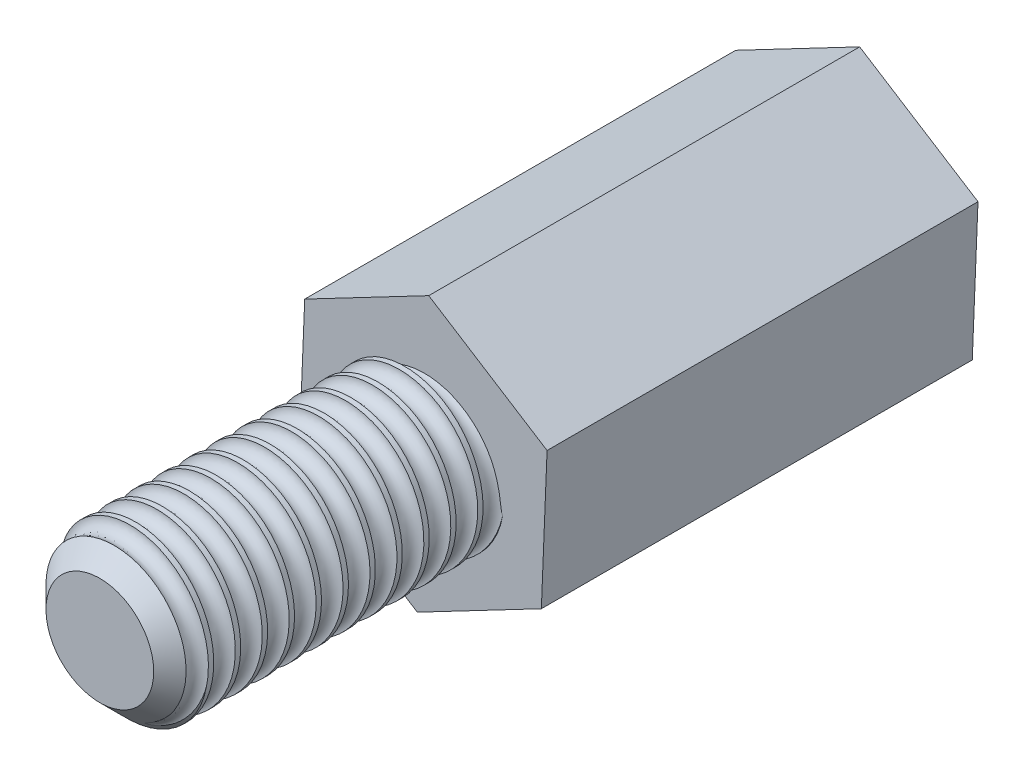
SolidWorks part; units mm, degrees
ref_plane "前视基准面" through (0, 0, 0) normal (0, 0, 1) x (1, 0, 0)
ref_plane "上视基准面" through (0, 0, 0) normal (0, 1, 0) x (1, 0, 0)
ref_plane "右视基准面" through (0, 0, 0) normal (1, 0, 0) x (0, 0, -1)
sketch "草图1" plane through (0, 0, 0) normal (0, 0, 1) x (1, 0, 0)
  line L1 (2.3029, 1.2069) -> (0.1062, 2.5978)
  line L2 (0.1062, 2.5978) -> (-2.1967, 1.3909)
  line L3 (-2.1967, 1.3909) -> (-2.3029, -1.2069)
  line L4 (-2.3029, -1.2069) -> (-0.1062, -2.5978)
  line L5 (-0.1062, -2.5978) -> (2.1967, -1.3909)
  line L6 (2.1967, -1.3909) -> (2.3029, 1.2069)
  circle A0 centre (0, 0) radius 2.6 construction
  dimension "D1" = 5.2
extrude "凸台-拉伸1" add sketch "草图1" along normal blind 8
sketch "草图2" plane through (0, 0, 8) normal (0, 0, 1) x (1, 0, 0)
  circle A0 centre (0, 0) radius 1.5
  dimension "D1" = 3
extrude "凸台-拉伸2" add sketch "草图2" along normal blind 6
chamfer "倒角1" distance 0.5 angle 45 1 edges at (1.5, 0, 14)
sketch "草图3" plane through (0, 0, 8) normal (0, 0, 1) x (1, 0, 0)
  circle A0 centre (0, 0) radius 1.5
  dimension "D1" = 3
curve "螺旋线/涡状线1" pitch 0.5 height 5.5 turns 11
ref_plane "基准面1" through (-1.0607, 1.0607, 13.5) normal (0.7061, 0.7061, 0.053) x (0.0375, 0.0375, -0.9986)
sketch "草图4" plane through (-1.0607, 1.0607, 13.5) normal (0.7061, 0.7061, 0.053) x (0.0375, 0.0375, -0.9986)
  circle A0 centre (0, 0) radius 0.2
  dimension "D1" = 0.4
sweep "切除-扫描1" cut profiles "草图4" path "螺旋线/涡状线1"
hole_wizard "M3 螺纹孔1" positions "草图6" profile "草图5" tap size "M3" standard "GB"
sketch "草图6" plane through (0, 0, 0) normal (0, 0, -1) x (-1, 0, 0)
  point P0 (0, 0)
sketch "草图5" plane through (0, 0, 0) normal (1, 0, 0) x (0, 1, 0)
  line L0 (0, 0) -> (0, 5.7511)
  line L1 (0, 5.7511) -> (1.25, 5)
  line L2 (1.25, 5) -> (1.25, 0)
  line L5 (1.25, 0) -> (0, 0)
  line L10 (0, 5.7511) -> (-1.25, 5) construction
  line L11 (0, -6.35) -> (0, 107.95) construction
  dimension "螺纹孔钻头直径" = 2.5
  dimension "螺纹孔钻头深度" = 5
  dimension "导头角度" = 118
cosmetic thread "孔螺蚊线1" parameters "D1"=5, "D2"=3
